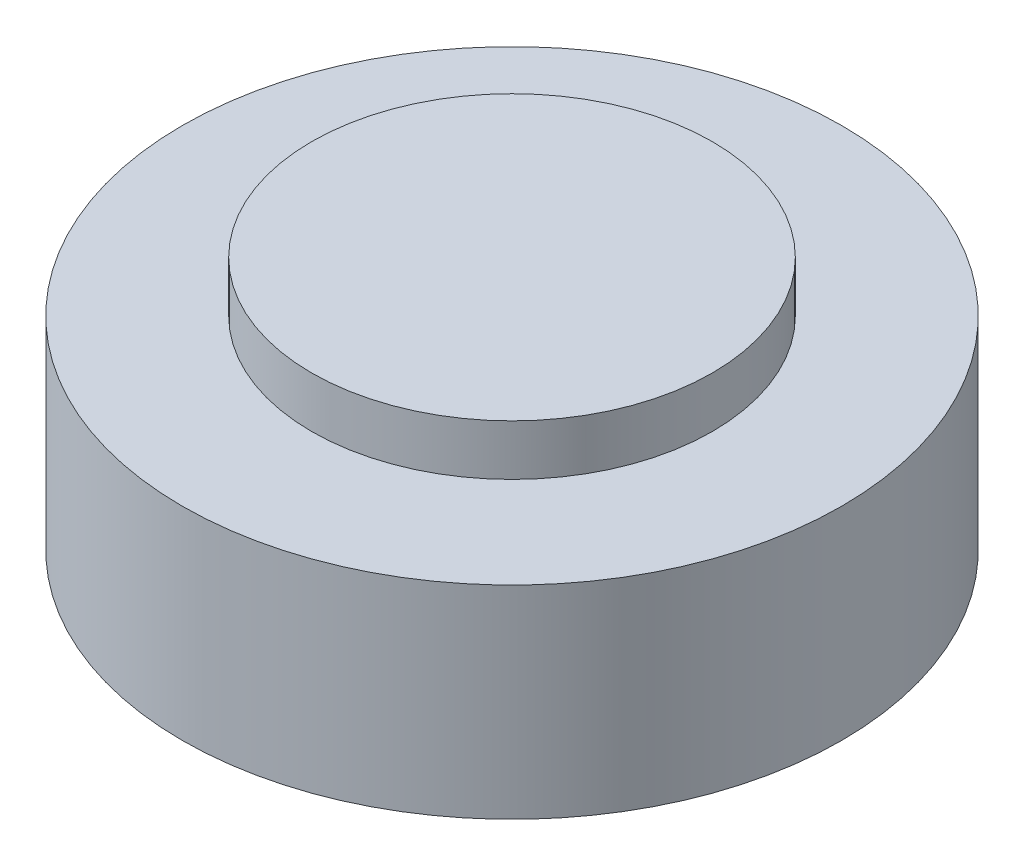
SolidWorks part; units mm, degrees
ref_plane "Front Plane" through (0, 0, 0) normal (0, 0, 1) x (1, 0, 0)
ref_plane "Top Plane" through (0, 0, 0) normal (0, 1, 0) x (1, 0, 0)
ref_plane "Right Plane" through (0, 0, 0) normal (1, 0, 0) x (0, 0, -1)
sketch "Croquis2" plane through (0, 0, 0) normal (0, 1, 0) x (1, 0, 0)
  circle A0 centre (0, 0) radius 7.9
  circle A1 centre (0, 0) radius 13
  dimension "D1" = 15.8
  dimension "D2" = 26
extrude "Saliente-Extruir1" add sketch "Croquis2" along normal blind 2 contours A0
extrude "Saliente-Extruir2" add sketch "Croquis2<3>" against normal blind 8 contours A0 | A1 A0 region at (0, 0, 0) region at (-12.6323, 0, 0)
sketch "Croquis2<3>" plane through (0, 0, 0) normal (0, 1, 0) x (1, 0, 0) same geometry as "Croquis2"
